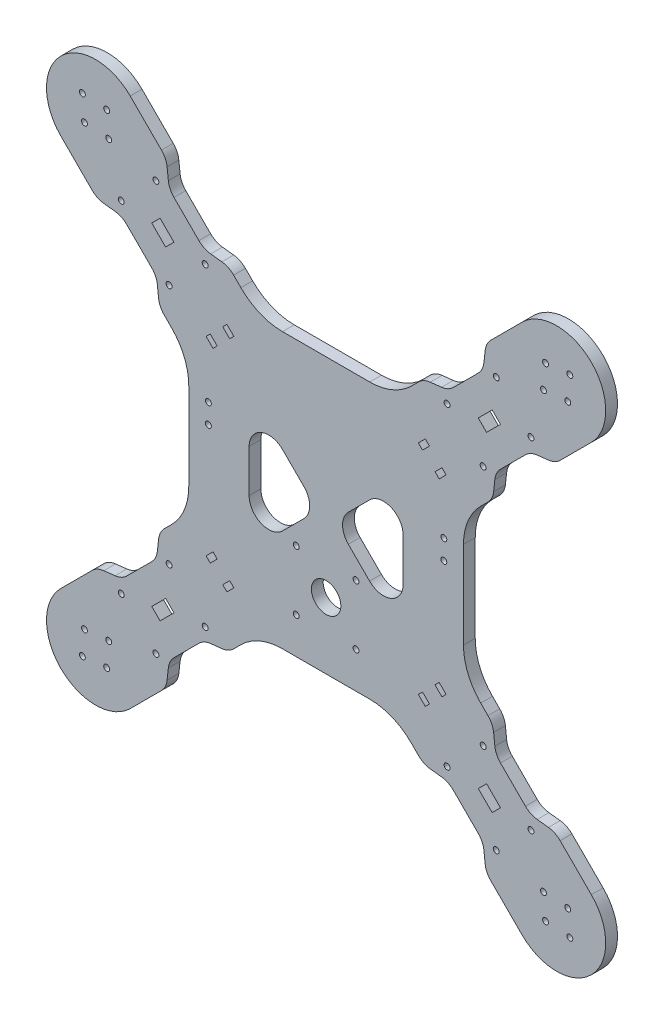
SolidWorks part; units mm, degrees
ref_plane "Front Plane" through (0, 0, 0) normal (0, 0, 1) x (1, 0, 0)
ref_plane "Top Plane" through (0, 0, 0) normal (0, 1, 0) x (1, 0, 0)
ref_plane "Right Plane" through (0, 0, 0) normal (1, 0, 0) x (0, 0, -1)
sketch "Sketch4" plane through (0, 0, 0) normal (0, 0, 1) x (1, 0, 0)
  line L0 (-117.5, 117.5) -> (117.5, -117.5) construction
  line L1 (-117.5, -117.5) -> (117.5, 117.5) construction
  line L2 (-1000, 0) -> (49000, 0) construction
  line L3 (0, -1000) -> (0, 49000) construction
  line L4 (-70, -34.6447) -> (-70, 34.6447)
  line L5 (34.6447, 70) -> (-34.6447, 70)
  line L6 (-70, 34.6447) -> (-135.1777, 99.8223)
  line L7 (-34.6447, 70) -> (-99.8223, 135.1777)
  line L8 (-135.1777, 99.8223) -> (-99.8223, 135.1777) construction
  line L9 (70, -34.6447) -> (70, 34.6447)
  line L10 (70, 34.6447) -> (135.1777, 99.8223)
  line L11 (34.6447, 70) -> (99.8223, 135.1777)
  line L12 (70, -34.6447) -> (135.1777, -99.8223)
  line L13 (34.6447, -70) -> (99.8223, -135.1777)
  line L14 (34.6447, -70) -> (-34.6447, -70)
  line L15 (-34.6447, -70) -> (-99.8223, -135.1777)
  line L16 (-70, -34.6447) -> (-135.1777, -99.8223)
  line L17 (-124.5711, 89.2157) -> (-89.2157, 124.5711) construction
  line L18 (-120.3284, 84.9731) -> (-84.9731, 120.3284) construction
  arc A0 (-135.1777, 99.8223) -> (-99.8223, 135.1777) centre (-117.5, 117.5) cw
  arc A1 (135.1777, 99.8223) -> (99.8223, 135.1777) centre (117.5, 117.5) ccw
  arc A2 (135.1777, -99.8223) -> (99.8223, -135.1777) centre (117.5, -117.5) cw
  arc A3 (-135.1777, -99.8223) -> (-99.8223, -135.1777) centre (-117.5, -117.5) ccw
  point P13 (-117.5, 117.5)
  point P17 (-135.1777, 135.1777)
  point P19 (0, 70)
  point P24 (70, 0)
  point P31 (-70, 0)
  point P34 (0, 0)
  point P35 (0, 0)
  dimension "D6" = 40
  dimension "D1" = 235
  dimension "D2" = 235
  dimension "D3" = 70
  dimension "D4" = 70
  dimension "D5" = 50
  dimension "D7" = 6
extrude "Boss-Extrude1" add sketch "Sketch4" along normal blind 6
fillet "Fillet1" radius 30 8 edges at (34.6447, -70, 3) (70, -34.6447, 3) (70, 34.6447, 3) (34.6447, 70, 3) (-34.6447, 70, 3) (-70, 34.6447, 3) (-70, -34.6447, 3) (-34.6447, -70, 3)
sketch "Sketch8" plane through (0, 0, 6) normal (0, 0, 1) x (1, 0, 0)
  line L0 (-120.3284, 84.9731) -> (-84.9731, 120.3284) construction
  line L1 (-117.5, 117.5) -> (117.5, -117.5) construction
  line L2 (-88.8622, 84.6195) -> (-84.6195, 88.8622)
  line L3 (-88.8622, 84.6195) -> (-81.7911, 77.5485)
  line L4 (-84.6195, 88.8622) -> (-77.5485, 81.7911)
  line L5 (-81.7911, 77.5485) -> (-77.5485, 81.7911)
  circle A0 centre (-104.4185, 86.7409) radius 1.5
  circle A2 centre (-80.0233, 61.6386) radius 1.5
  circle A4 centre (-86.7409, 104.4185) radius 1.5
  circle A5 centre (-61.6386, 80.0233) radius 1.5
  dimension "D1" = 3
  dimension "D2" = 10
  dimension "D3" = 12.5
  dimension "D4" = 13
  dimension "D5" = 45
  dimension "D6" = 10
  dimension "D7" = 12.5
  dimension "D8" = 45
  dimension "D9" = 13
  dimension "D10" = 6
  dimension "D11" = 3
  dimension "D12" = 22.5
  dimension "D13" = 10
sketch "Sketch9" plane through (0, 0, 6) normal (0, 0, 1) x (1, 0, 0)
  line L0 (-135.1777, 99.8223) -> (-99.8223, 135.1777) construction
  line L1 (-117.5, 117.5) -> (117.5, -117.5) construction
  circle A0 centre (-124.2175, 124.2175) radius 1.5
  circle A1 centre (-110.7825, 110.7825) radius 1.5
  circle A2 centre (-123.1569, 111.8431) radius 1.5
  circle A3 centre (-111.8431, 123.1569) radius 1.5
  dimension "D5" = 3
  dimension "D1" = 8
  dimension "D2" = 8
  dimension "D3" = 9.5
  dimension "D4" = 9.5
extrude "Cut-Extrude1" cut sketch "Sketch8" against normal through all both and the other way through all
extrude "Cut-Extrude2" cut sketch "Sketch9" against normal through all both and the other way through all
mirror "Mirror1" about plane through (0, 0, 0) normal (1, 0, 0) of "Cut-Extrude2", "Cut-Extrude1"
mirror "Mirror2" about plane through (0, 0, 0) normal (0, 1, 0) of "Mirror1"
sketch "Sketch10" plane through (0, 0, 6) normal (0, 0, 1) x (1, 0, 0)
  line L0 (-70, -34.6447) -> (-70, 34.6447) construction
  line L1 (70, -34.6447) -> (70, 34.6447) construction
  line L2 (34.6447, 70) -> (-34.6447, 70) construction
  line L3 (-49.1421, -53.3848) -> (-47.0208, -55.5061)
  line L4 (0, -201000) -> (0, 249000) construction
  line L5 (-201000, 0) -> (249000, 0) construction
  line L6 (-4.2426, 0) -> (-39.2426, 35)
  line L7 (-39.2426, 35) -> (-39.2426, -35)
  line L8 (-39.2426, -35) -> (-4.2426, 0)
  line L9 (-117.5, 117.5) -> (117.5, -117.5) construction
  line L10 (-117.5, -117.5) -> (117.5, 117.5) construction
  line L11 (0, -3.3) -> (0, 3.3) construction
  line L12 (39.2426, 35) -> (39.2426, -35)
  line L13 (4.2426, 0) -> (39.2426, 35)
  line L14 (39.2426, -35) -> (4.2426, 0)
  line L21 (3.3, 0) -> (-3.3, 0) construction
  line L22 (-57.6274, -44.8995) -> (-55.5061, -47.0208)
  line L23 (-59.0416, -50.5563) -> (-55.5061, -47.0208)
  line L24 (-61.163, -48.435) -> (-59.0416, -50.5563)
  line L25 (-61.163, 48.435) -> (-59.0416, 50.5563)
  line L26 (-61.163, 48.435) -> (-57.6274, 44.8995)
  line L27 (-57.6274, 44.8995) -> (-55.5061, 47.0208)
  line L28 (-59.0416, 50.5563) -> (-55.5061, 47.0208)
  line L29 (-61.163, -48.435) -> (-57.6274, -44.8995)
  line L30 (57.6274, 44.8995) -> (55.5061, 47.0208)
  line L31 (59.0416, 50.5563) -> (55.5061, 47.0208)
  line L32 (61.163, 48.435) -> (59.0416, 50.5563)
  line L33 (61.163, 48.435) -> (57.6274, 44.8995)
  line L34 (61.163, -48.435) -> (57.6274, -44.8995)
  line L35 (61.163, -48.435) -> (59.0416, -50.5563)
  line L36 (59.0416, -50.5563) -> (55.5061, -47.0208)
  line L37 (57.6274, -44.8995) -> (55.5061, -47.0208)
  line L38 (-52.6777, 56.9203) -> (-50.5563, 59.0416)
  line L39 (-52.6777, 56.9203) -> (-49.1421, 53.3848)
  line L40 (-49.1421, 53.3848) -> (-47.0208, 55.5061)
  line L41 (-50.5563, 59.0416) -> (-47.0208, 55.5061)
  line L42 (-50.5563, -59.0416) -> (-47.0208, -55.5061)
  line L43 (-52.6777, -56.9203) -> (-50.5563, -59.0416)
  line L44 (-52.6777, -56.9203) -> (-49.1421, -53.3848)
  line L45 (52.6777, -56.9203) -> (49.1421, -53.3848)
  line L46 (52.6777, -56.9203) -> (50.5563, -59.0416)
  line L47 (50.5563, -59.0416) -> (47.0208, -55.5061)
  line L48 (49.1421, -53.3848) -> (47.0208, -55.5061)
  line L49 (49.1421, 53.3848) -> (47.0208, 55.5061)
  line L50 (50.5563, 59.0416) -> (47.0208, 55.5061)
  line L51 (52.6777, 56.9203) -> (50.5563, 59.0416)
  line L52 (52.6777, 56.9203) -> (49.1421, 53.3848)
  line L53 (-15.25, -21) -> (15.25, -51.5) construction
  circle A0 centre (-60, 20) radius 1.5
  circle A1 centre (-60, 10) radius 1.5
  circle A2 centre (60, 20) radius 1.5
  circle A3 centre (60, 10) radius 1.5
  circle A4 centre (-15.25, -21) radius 1.5
  circle A5 centre (15.25, -21) radius 1.5
  circle A6 centre (-15.25, -51.5) radius 1.5
  circle A7 centre (15.25, -51.5) radius 1.5
  circle A8 centre (0, -36.25) radius 7.5
  point P56 (0, 0)
  point P75 (0, 0)
  dimension "D2" = 10
  dimension "D5" = 3
  dimension "D8" = 3
  dimension "D17" = 15
  dimension "D1" = 10
  dimension "D3" = 10
  dimension "D4" = 50
  dimension "D6" = 30.5
  dimension "D7" = 30.5
  dimension "D9" = 15.25
  dimension "D10" = 21
  dimension "D11" = 3
  dimension "30" = 35
  dimension "D12" = 6
  dimension "D13" = 3
  dimension "D14" = 5
  dimension "D15" = 20
  dimension "D16" = 3
extrude "Cut-Extrude3" cut sketch "Sketch10" against normal through all both and the other way through all
fillet "Fillet2" radius 10 6 edges at (4.2426, 0, 3) (39.2426, -35, 3) (39.2426, 35, 3) (-39.2426, -35, 3) (-39.2426, 35, 3) (-4.2426, 0, 3)
sketch "Sketch11" plane through (0, 0, 6) normal (0, 0, 1) x (1, 0, 0)
  line L1 (-34.6447, 70) -> (-99.8223, 135.1777) construction
  line L2 (-80.0233, 104.065) -> (-62.3457, 86.3873)
  line L3 (-62.3457, 86.3873) -> (-49.6177, 84.9731)
  line L4 (-49.6177, 84.9731) -> (-81.4376, 116.7929)
  line L5 (-81.4376, 116.7929) -> (-80.0233, 104.065)
  line L6 (-80.0233, 104.065) -> (-74.3665, 109.7218) construction
  line L7 (-62.3457, 86.3873) -> (-56.6888, 92.0442) construction
  line L8 (-120.3284, 84.9731) -> (-84.9731, 120.3284) construction
  dimension "D1" = 45
  dimension "D2" = 8
  dimension "D3" = 10
  dimension "D4" = 10
  dimension "D5" = 5
extrude "Cut-Extrude4" cut sketch "Sketch11" against normal through all both and the other way through all
ref_plane "Plane1" through (0, 0, 0) normal (0.7071, 0.7071, 0) x (0.7071, -0.7071, 0)
mirror "Mirror4" about plane through (0, 0, 0) normal (0.7071, 0.7071, 0) of "Cut-Extrude4"
ref_axis "Axis1" through (0, 0, 0) along (0, 0, 1)
pattern_circular "CirPattern2" count 4 over 360 about axis through (0, 0, 0) along (0, 0, 1) of "Cut-Extrude4", "Mirror4"
fillet "Fillet3" radius 10 32 edges at (-49.6177, 84.9731, 3) (-62.3457, 86.3873, 3) (-80.0233, 104.065, 3) (-81.4376, 116.7929, 3) (116.7929, 81.4376, 3) (104.065, 80.0233, 3) (86.3873, 62.3457, 3) (84.9731, 49.6177, 3) (80.0233, 104.065, 3) (81.4376, 116.7929, 3) (62.3457, 86.3873, 3) (49.6177, 84.9731, 3) (116.7929, -81.4376, 3) (104.065, -80.0233, 3) (86.3873, -62.3457, 3) (84.9731, -49.6177, 3) (81.4376, -116.7929, 3) (80.0233, -104.065, 3) (62.3457, -86.3873, 3) (49.6177, -84.9731, 3) (-49.6177, -84.9731, 3) (-62.3457, -86.3873, 3) (-80.0233, -104.065, 3) (-81.4376, -116.7929, 3) (-116.7929, -81.4376, 3) (-104.065, -80.0233, 3) (-86.3873, -62.3457, 3) (-84.9731, -49.6177, 3) (-84.9731, 49.6177, 3) (-86.3873, 62.3457, 3) (-104.065, 80.0233, 3) (-116.7929, 81.4376, 3)
equation "\"D6@Sketch8\"=\"D2@Sketch8\""
equation "\"D7@Sketch8\"=\"D3@Sketch8\""
equation "\"D8@Sketch8\"=\"D5@Sketch8\""
equation "\"D9@Sketch8\"=\"D4@Sketch8\""
equation "\"D2@Sketch9\"=\"D1@Sketch9\""
equation "\"D4@Sketch9\"=\"D3@Sketch9\""
equation "\"D9@Sketch10\"=\"D6@Sketch10\"/2"
